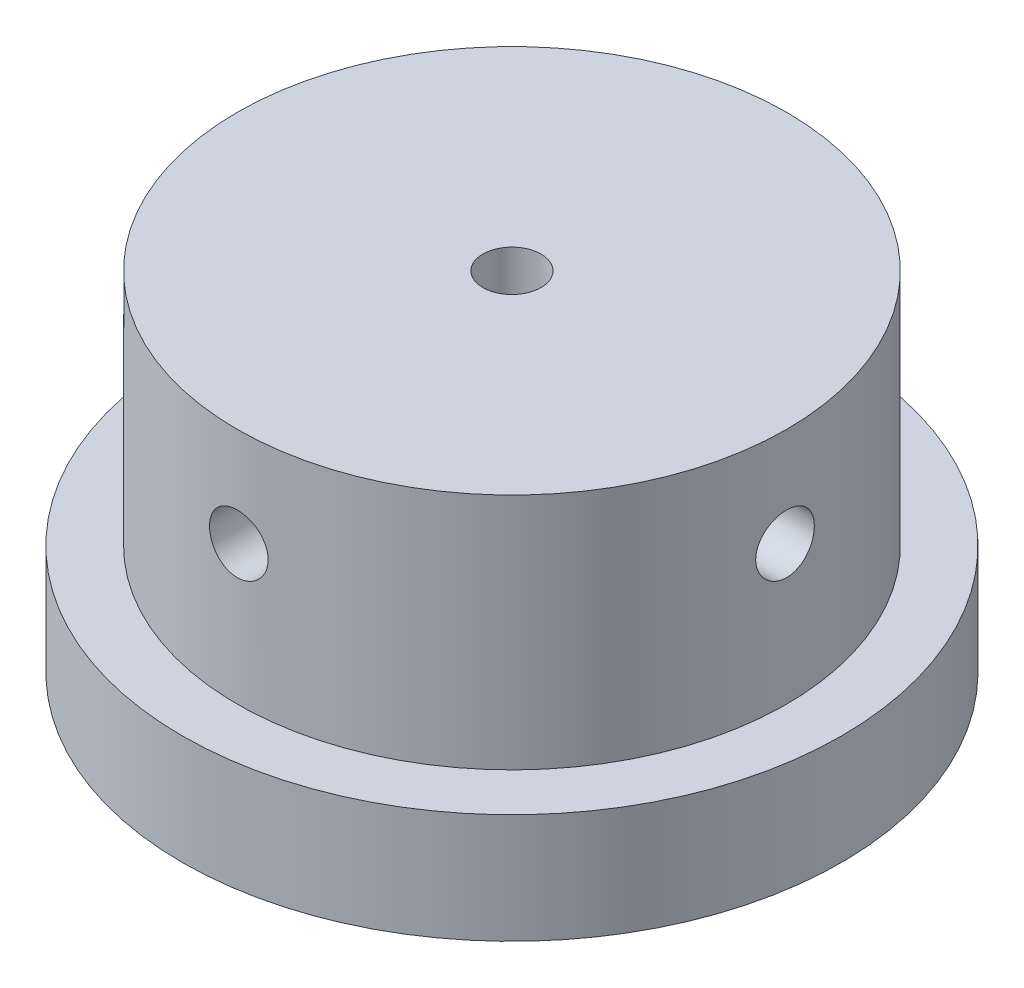
SolidWorks part; units mm, degrees
ref_plane "Front Plane" through (0, 0, 0) normal (0, 0, 1) x (1, 0, 0)
ref_plane "Top Plane" through (0, 0, 0) normal (0, 1, 0) x (1, 0, 0)
ref_plane "Right Plane" through (0, 0, 0) normal (1, 0, 0) x (0, 0, -1)
sketch "Sketch1" plane through (0, 0, 0) normal (0, 1, 0) x (1, 0, 0)
  circle A0 centre (0, 0) radius 15
  dimension "D1" = 30
extrude "Boss-Extrude1" add sketch "Sketch1" along normal blind 2
sketch "Sketch2" plane through (0, 2, 0) normal (0, 1, 0) x (1, 0, 0)
  circle A0 centre (0, 0) radius 13.5
  circle A1 centre (0, 0) radius 15
  circle A2 centre (0, 0) radius 15
  dimension "D1" = 0
  dimension "D2" = 1.5
extrude "Boss-Extrude2" add sketch "Sketch2" against normal up to surface (13 mm away)
sketch "Sketch3" plane through (0, -11, 0) normal (0, -1, 0) x (1, 0, 0)
  circle A0 centre (0, 0) radius 13.5 construction
  circle A1 centre (0, 0) radius 13.5
  circle A2 centre (0, 0) radius 18
  dimension "D1" = 36
extrude "Boss-Extrude3" add sketch "Sketch3" along normal up to surface (2 mm away)
sketch "Sketch4" plane through (0, -13, 0) normal (0, -1, 0) x (1, 0, 0)
  circle A0 centre (0, 0) radius 16.1
  circle A1 centre (0, 0) radius 18
  circle A2 centre (0, 0) radius 18
  dimension "D2" = 32.2
  dimension "D1" = 0
extrude "Boss-Extrude4" add sketch "Sketch4" along normal up to surface (3.9878 mm away)
chamfer "Chamfer1" distance 1 angle 45 1 edges at (0, -13, 13.5)
sketch "Sketch5" plane through (0, 2, 0) normal (0, 1, 0) x (1, 0, 0)
  circle A0 centre (0, 0) radius 13.5
  circle A1 centre (0, 0) radius 13.5 construction
extrude "Boss-Extrude5" add sketch "Sketch5" against normal up to surface (8.8216 mm away)
sketch "Sketch6" plane through (0, 2, 0) normal (0, 1, 0) x (1, 0, 0)
  circle A0 centre (0, 0) radius 1.5875
  dimension "D1" = 3.175
extrude "Cut-Extrude1" cut sketch "Sketch6" against normal through all both and the other way through all
sketch "Sketch7" plane through (0, 0, 0) normal (1, 0, 0) x (0, 0, -1)
  line L0 (0, 0) -> (0, -6.8216) construction
  line L1 (-1.5875, -6.8216) -> (1.5875, -6.8216) construction
  circle A0 centre (0, -3.4108) radius 1.6
  dimension "D1" = 3.2
extrude "Cut-Extrude2" cut sketch "Sketch7" against normal through all
ref_axis "Axis1" through (0, -12, 0) along (0, 1, 0)
ref_plane "Plane2" through (-10, 0, 0) normal (1, 0, 0) x (0, 0, -1)
ref_plane "Plane3" through (-9, 0, 0) normal (1, 0, 0) x (0, 0, -1)
sketch "Sketch11" plane through (-10, 0, 0) normal (1, 0, 0) x (0, 0, -1)
  circle A0 centre (0, -3.4108) radius 1.6 construction
  circle A1 centre (0, -3.4108) radius 1.6 construction
  circle A2 centre (0, -3.4108) radius 2
  dimension "D1" = 4
extrude "Cut-Extrude7" [suppressed] cut sketch "Sketch11" along normal blind 5.5
sketch "Sketch12" plane through (-10, 0, 0) normal (1, 0, 0) x (0, 0, -1)
  circle A0 centre (0, -3.4108) radius 3.5
  dimension "D1" = 7
extrude "Cut-Extrude8" [suppressed] cut sketch "Sketch12" against normal blind 5
chamfer "Chamfer2" [suppressed] distance 1 angle 45
pattern_circular "CirPattern3" count 4 over 360 about axis through (0, -12, 0) along (0, 1, 0) of "Cut-Extrude2", "Cut-Extrude7", "Cut-Extrude8", "Chamfer2"
sketch "Sketch13" plane through (-9, 0, 0) normal (1, 0, 0) x (0, 0, -1)
  line L0 (-2.75, -4.9985) -> (-2.75, -6.8216)
  line L1 (0, -6.5862) -> (2.75, -4.9985) construction
  line L2 (2.75, -4.9985) -> (2.75, -1.8231)
  line L3 (2.75, -1.8231) -> (0, -0.2354)
  line L4 (0, -0.2354) -> (-2.75, -1.8231)
  line L5 (-2.75, -1.8231) -> (-2.75, -4.9985)
  line L6 (-2.75, -4.9985) -> (0, -6.5862) construction
  line L7 (-2.75, -6.8216) -> (2.75, -6.8216)
  line L8 (2.75, -6.8216) -> (2.75, -4.9985)
  line L9 (-1.5875, -6.8216) -> (1.5875, -6.8216) construction
  circle A0 centre (0, -3.4108) radius 2.75 construction
  circle A1 centre (0, -3.4108) radius 1.6 construction
  dimension "D1" = 5.5
extrude "Cut-Extrude9" cut sketch "Sketch13" along normal blind 3
pattern_circular "CirPattern4" count 4 over 360 about axis through (0, -12, 0) along (0, 1, 0) of "Cut-Extrude9"
